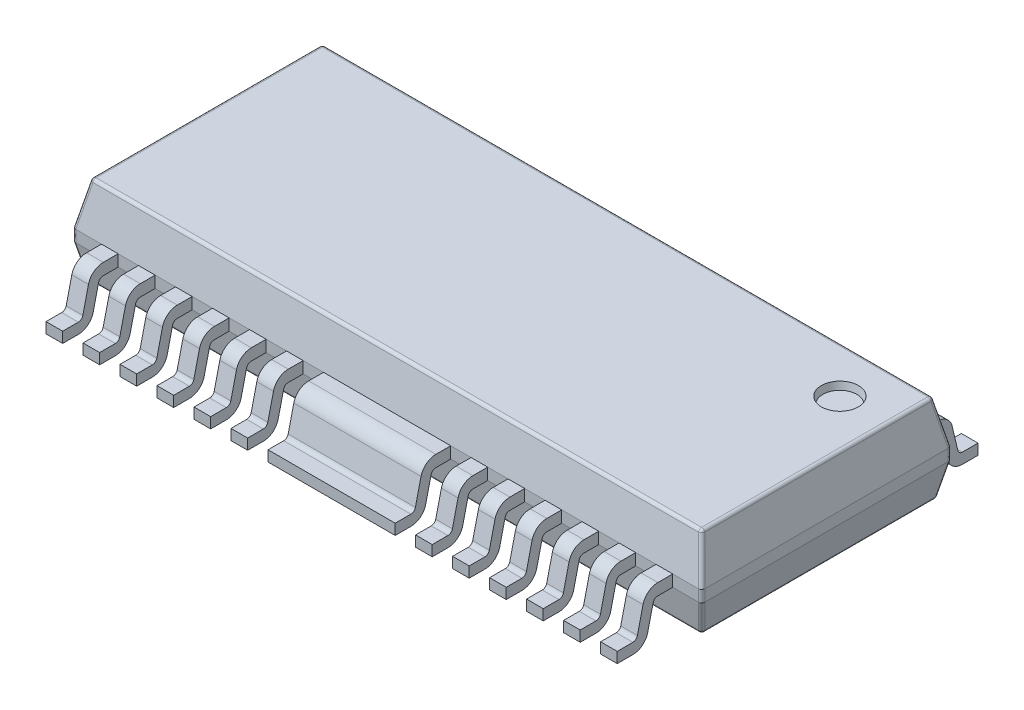
SolidWorks part; units mm, degrees
note: '?' marks a value the reader was unsure of.
ref_plane "Front Plane" through (0, 0, 0) normal (0, 0, 1) x (1, 0, 0)
ref_plane "Top Plane" through (0, 0, 0) normal (0, 1, 0) x (1, 0, 0)
ref_plane "Right Plane" through (0, 0, 0) normal (1, 0, 0) x (0, 0, -1)
ref_axis "Axis1" through (7.48, 0, 0) along (-1, 0, 0)?
ref_plane "Plane1" through (-1.995, 0, 0) normal (1, 0, 0) x (0, 0, -1)
ref_plane "Plane2" through (1.995, 0, 0) normal (1, 0, 0) x (0, 0, -1)
sketch "Sketch1" plane through (0, 0, 0) normal (0, 1, 0) x (1, 0, 0)
  line L1 (-6.8, 2.7) -> (6.8, 2.7)
  line L2 (-6.8, 2.7) -> (-6.8, -2.7)
  line L3 (-6.8, -2.7) -> (6.8, -2.7)
  line L4 (6.8, 2.7) -> (6.8, -2.7)
  dimension "D1" = 13.6
  dimension "D2" = 5.4
  dimension "D3" = 6.8
  dimension "D4" = 2.7
extrude "Extrude1" add sketch "Sketch1" along normal blind 0.93 draft 12 and the other way blind 0.25
sketch "Sketch2" plane through (0, -0.25, 0) normal (0, -1, 0) x (1, 0, 0)
  line L4 (-6.8, 2.7) -> (-6.8, -2.7)
  line L5 (-6.8, -2.7) -> (6.8, -2.7)
  line L6 (6.8, -2.7) -> (6.8, 2.7)
  line L7 (6.8, 2.7) -> (-6.8, 2.7)
  line L8 (-6.8, 2.7) -> (-6.8, -2.7)
  line L9 (-6.8, -2.7) -> (6.8, -2.7)
  line L10 (6.8, -2.7) -> (6.8, 2.7)
  line L11 (6.8, 2.7) -> (-6.8, 2.7)
  dimension "D1" = 0
extrude "Extrude2" add sketch "Sketch2" along normal blind 0.72 draft 12
sketch "Sketch3" plane through (0, 0.93, 0) normal (0, 1, 0) x (-1, 0, 0)
  circle A0 centre (-5.5841, -1.505) radius 0.4
extrude "Cut-Extrude1" cut sketch "Sketch3" against normal blind 0.15 draft 12
sketch "Sketch4" plane through (-1.995, 0, 0) normal (1, 0, 0) x (0, 0, -1)
  line L0 (2.7, -0.25) -> (-2.7, -0.25) construction
  line L1 (2.7, 0) -> (-2.7, 0) construction
  line L2 (2.7, -0.25) -> (-2.7, -0.25)
  line L3 (2.7, 0) -> (-2.7, 0)
  line L4 (-2.547, -0.97) -> (2.547, -0.97) construction
  line L5 (3.9, -0.85) -> (3.4822, -0.85)
  line L6 (3.9, -0.85) -> (3.9, -1.08)
  line L7 (3.9, -1.08) -> (3.3, -1.08)
  line L8 (3.6, -0.85) -> (3.6, -1.08) construction
  line L9 (-2.155, -0.85) -> (-3.4822, -0.85) construction
  line L10 (-2.155, -0.85) -> (-2.155, -1.08) construction
  line L11 (-2.155, -1.08) -> (-3.3, -1.08) construction
  line L12 (-3.9, -0.85) -> (-3.9, -1.08)
  line L13 (2.7, 0) -> (3.2822, 0)
  line L14 (2.6703, 0) -> (2.6703, -0.25) construction
  line L15 (2.6703, -0.25) -> (3.1047, -0.25) construction
  line L16 (-2.7, 0) -> (-3.2822, 0)
  line L17 (-2.6934, 0) -> (-2.6934, -0.25) construction
  line L18 (-2.6934, -0.25) -> (-3.1047, -0.25) construction
  line L19 (3.2822, 0) -> (2.6703, 0) construction
  line L20 (3.4822, -0.85) -> (3.2822, 0)
  line L21 (3.3, -1.08) -> (3.1047, -0.25)
  line L22 (3.1047, -0.25) -> (2.7, -0.25)
  line L23 (3.3, -1.08) -> (3.6, -1.08) construction
  line L24 (3.4822, -0.85) -> (3.6, -0.85) construction
  line L25 (0, -1.1578) -> (0, -1.9582) construction
  line L26 (-3.3, -1.08) -> (-3.1047, -0.25)
  line L27 (-3.4822, -0.85) -> (-3.2822, 0)
  line L28 (-3.1047, -0.25) -> (-2.7, -0.25)
  line L29 (-3.2822, 0) -> (-2.6934, 0) construction
  line L30 (-3.4822, -0.85) -> (-3.9, -0.85)
  line L31 (-3.3, -1.08) -> (-3.9, -1.08)
  dimension "D1" = 0.3
  dimension "D2" = 7.8
  dimension "D3" = 3.9
  dimension "D4" = 0.11
  dimension "D5" = 0.23
  dimension "D6" = 0.23
  dimension "D7" = 0.6
  dimension "D8" = 0.2
extrude "Extrude3" add sketch "Sketch4" along normal blind 0.18 and the other way blind 0.18
pattern_linear "LPattern3" count 1 spacing 0.8 along (-1, 0, 0) count 6 spacing 0.8 along (-1, 0, 0) of "Extrude3"
sketch "Sketch5" plane through (1.995, 0, 0) normal (1, 0, 0) x (0, 0, -1)
  line L16 (3.9, -0.85) -> (3.4822, -0.85)
  line L17 (3.9, -1.08) -> (3.9, -0.85)
  line L18 (3.3, -1.08) -> (3.9, -1.08)
  line L19 (3.1047, -0.25) -> (3.3, -1.08)
  line L20 (2.7, -0.25) -> (3.1047, -0.25)
  line L21 (-2.7, -0.25) -> (2.7, -0.25)
  line L22 (-3.1047, -0.25) -> (-2.7, -0.25)
  line L23 (-3.3, -1.08) -> (-3.1047, -0.25)
  line L24 (-3.9, -1.08) -> (-3.3, -1.08)
  line L25 (-3.9, -0.85) -> (-3.9, -1.08)
  line L26 (-3.4822, -0.85) -> (-3.9, -0.85)
  line L27 (-3.2822, 0) -> (-3.4822, -0.85)
  line L28 (-2.7, 0) -> (-3.2822, 0)
  line L29 (2.7, 0) -> (-2.7, 0)
  line L30 (3.2822, 0) -> (2.7, 0)
  line L31 (3.4822, -0.85) -> (3.2822, 0)
  line L32 (3.9, -0.85) -> (3.4822, -0.85)
  line L33 (3.9, -1.08) -> (3.9, -0.85)
  line L34 (3.3, -1.08) -> (3.9, -1.08)
  line L35 (3.1047, -0.25) -> (3.3, -1.08)
  line L36 (2.7, -0.25) -> (3.1047, -0.25)
  line L37 (-2.7, -0.25) -> (2.7, -0.25)
  line L38 (-3.1047, -0.25) -> (-2.7, -0.25)
  line L39 (-3.3, -1.08) -> (-3.1047, -0.25)
  line L40 (-3.9, -1.08) -> (-3.3, -1.08)
  line L41 (-3.9, -0.85) -> (-3.9, -1.08)
  line L42 (-3.4822, -0.85) -> (-3.9, -0.85)
  line L43 (-3.2822, 0) -> (-3.4822, -0.85)
  line L44 (-2.7, 0) -> (-3.2822, 0)
  line L45 (2.7, 0) -> (-2.7, 0)
  line L46 (3.2822, 0) -> (2.7, 0)
  line L47 (3.4822, -0.85) -> (3.2822, 0)
  dimension "D1" = 0
sketch "Sketch6" plane through (0, 0, 0) normal (1, 0, 0) x (0, 0, -1)
  line L16 (3.9, -0.85) -> (3.4822, -0.85)
  line L17 (3.9, -1.08) -> (3.9, -0.85)
  line L18 (3.3, -1.08) -> (3.9, -1.08)
  line L19 (3.1047, -0.25) -> (3.3, -1.08)
  line L20 (2.7, -0.25) -> (3.1047, -0.25)
  line L21 (-2.7, -0.25) -> (2.7, -0.25)
  line L22 (-3.1047, -0.25) -> (-2.7, -0.25)
  line L23 (-3.3, -1.08) -> (-3.1047, -0.25)
  line L24 (-3.9, -1.08) -> (-3.3, -1.08)
  line L25 (-3.9, -0.85) -> (-3.9, -1.08)
  line L26 (-3.4822, -0.85) -> (-3.9, -0.85)
  line L27 (-3.2822, 0) -> (-3.4822, -0.85)
  line L28 (-2.7, 0) -> (-3.2822, 0)
  line L29 (2.7, 0) -> (-2.7, 0)
  line L30 (3.2822, 0) -> (2.7, 0)
  line L31 (3.4822, -0.85) -> (3.2822, 0)
  line L32 (3.9, -0.85) -> (3.4822, -0.85)
  line L33 (3.9, -1.08) -> (3.9, -0.85)
  line L34 (3.3, -1.08) -> (3.9, -1.08)
  line L35 (3.1047, -0.25) -> (3.3, -1.08)
  line L36 (2.7, -0.25) -> (3.1047, -0.25)
  line L37 (-2.7, -0.25) -> (2.7, -0.25)
  line L38 (-3.1047, -0.25) -> (-2.7, -0.25)
  line L39 (-3.3, -1.08) -> (-3.1047, -0.25)
  line L40 (-3.9, -1.08) -> (-3.3, -1.08)
  line L41 (-3.9, -0.85) -> (-3.9, -1.08)
  line L42 (-3.4822, -0.85) -> (-3.9, -0.85)
  line L43 (-3.2822, 0) -> (-3.4822, -0.85)
  line L44 (-2.7, 0) -> (-3.2822, 0)
  line L45 (2.7, 0) -> (-2.7, 0)
  line L46 (3.2822, 0) -> (2.7, 0)
  line L47 (3.4822, -0.85) -> (3.2822, 0)
  dimension "D1" = 0
extrude "Extrude5" add sketch "Sketch6" along normal blind 1.375 and the other way blind 1.375
extrude "Extrude6" add sketch "Sketch5" along normal blind 0.18 and the other way blind 0.18
pattern_linear "LPattern4" count 6 spacing 0.8 along (1, 0, 0) of "Extrude6"
fillet "Fillet2" radius 0.33 52 edges at (-2.795, -1.08, -3.3) (-2.795, 0, 3.2822) (-2.795, -1.08, 3.3) (-3.595, 0, -3.2822) (-3.595, -1.08, -3.3) (-3.595, 0, 3.2822) (-3.595, -1.08, 3.3) (-4.395, 0, -3.2822) (-4.395, -1.08, -3.3) (-4.395, 0, 3.2822) (-4.395, -1.08, 3.3) (-5.195, 0, -3.2822) (-5.195, -1.08, -3.3) (-5.195, 0, 3.2822) (-5.195, -1.08, 3.3) (-5.995, 0, -3.2822) (-5.995, -1.08, -3.3) (-5.995, 0, 3.2822) (-5.995, -1.08, 3.3) (0, 0, -3.2822) (0, 0, 3.2822) (0, -1.08, 3.3) (0, -1.08, -3.3) (1.995, 0, -3.2822) (1.995, 0, 3.2822) (1.995, -1.08, 3.3) (1.995, -1.08, -3.3) (2.795, 0, -3.2822) (2.795, 0, 3.2822) (2.795, -1.08, 3.3) (2.795, -1.08, -3.3) (-1.995, 0, -3.2822) (3.595, 0, -3.2822) (3.595, 0, 3.2822) (3.595, -1.08, 3.3) (3.595, -1.08, -3.3) (4.395, 0, -3.2822) (4.395, 0, 3.2822) (4.395, -1.08, 3.3) (4.395, -1.08, -3.3) (-1.995, -1.08, -3.3) (5.195, 0, -3.2822) (-1.995, 0, 3.2822) (5.195, 0, 3.2822) (5.195, -1.08, 3.3) (5.195, -1.08, -3.3) (-1.995, -1.08, 3.3) (5.995, 0, -3.2822) (5.995, 0, 3.2822) (5.995, -1.08, 3.3) (5.995, -1.08, -3.3) (-2.795, 0, -3.2822)
fillet "Fillet1" radius 0.1 52 edges at (-1.995, -0.85, 3.4822) (-1.995, -0.25, 3.1047) (-1.995, -0.85, -3.4822) (-1.995, -0.25, -3.1047) (-4.395, -0.85, 3.4822) (-3.595, -0.85, 3.4822) (-2.795, -0.85, 3.4822) (-2.795, -0.85, -3.4822) (-3.595, -0.85, -3.4822) (-4.395, -0.85, -3.4822) (-4.395, -0.25, 3.1047) (-3.595, -0.25, 3.1047) (-2.795, -0.25, 3.1047) (-4.395, -0.25, -3.1047) (-3.595, -0.25, -3.1047) (-2.795, -0.25, -3.1047) (5.995, -0.25, 3.1047) (5.195, -0.25, 3.1047) (4.395, -0.25, 3.1047) (3.595, -0.25, 3.1047) (2.795, -0.25, 3.1047) (1.995, -0.25, 3.1047) (0, -0.25, 3.1047) (-5.995, -0.25, 3.1047) (-5.195, -0.25, 3.1047) (-5.995, -0.25, -3.1047) (-5.195, -0.25, -3.1047) (0, -0.25, -3.1047) (1.995, -0.25, -3.1047) (2.795, -0.25, -3.1047) (3.595, -0.25, -3.1047) (4.395, -0.25, -3.1047) (5.195, -0.25, -3.1047) (5.995, -0.25, -3.1047) (-5.995, -0.85, -3.4822) (-5.195, -0.85, -3.4822) (0, -0.85, -3.4822) (1.995, -0.85, -3.4822) (2.795, -0.85, -3.4822) (3.595, -0.85, -3.4822) (4.395, -0.85, -3.4822) (5.195, -0.85, -3.4822) (5.995, -0.85, -3.4822) (5.995, -0.85, 3.4822) (5.195, -0.85, 3.4822) (4.395, -0.85, 3.4822) (3.595, -0.85, 3.4822) (2.795, -0.85, 3.4822) (1.995, -0.85, 3.4822) (0, -0.85, 3.4822) (-5.195, -0.85, 3.4822) (-5.995, -0.85, 3.4822)
fillet "Fillet3" radius 0.07 20 edges at (6.6023, 0.93, 0) (-6.8, -0.125, 2.7) (0, 0.93, -2.5023) (-6.8, -0.125, -2.7) (6.8, -0.125, -2.7) (6.8, -0.125, 2.7) (6.7235, -0.61, 2.6235) (-6.7235, -0.61, 2.6235) (-6.7235, -0.61, -2.6235) (6.7235, -0.61, -2.6235) (0, -0.97, 2.547) (-6.647, -0.97, 0) (0, -0.97, -2.547) (6.647, -0.97, 0) (-6.6023, 0.93, 0) (0, 0.93, 2.5023) (-6.7012, 0.465, -2.6012) (6.7012, 0.465, -2.6012) (6.7012, 0.465, 2.6012) (-6.7012, 0.465, 2.6012)
ref_plane "Board Surface" through (0, -1.08, 0) normal (0, 1, 0) x (-1, 0, 0)
sketch "Component_Outline" plane through (0, -1.08, 0) normal (0, 1, 0) x (-1, 0, 0)
  line L0 (6.175, 3.9) -> (5.815, 3.9)
  line L1 (5.815, 3.9) -> (5.815, 2.7)
  line L2 (5.815, 2.7) -> (5.375, 2.7)
  line L3 (5.375, 2.7) -> (5.375, 3.9)
  line L4 (5.375, 3.9) -> (5.015, 3.9)
  line L5 (5.015, 3.9) -> (5.015, 2.7)
  line L6 (5.015, 2.7) -> (4.575, 2.7)
  line L7 (4.575, 2.7) -> (4.575, 3.9)
  line L8 (4.575, 3.9) -> (4.215, 3.9)
  line L9 (4.215, 3.9) -> (4.215, 2.7)
  line L10 (4.215, 2.7) -> (3.775, 2.7)
  line L11 (3.775, 2.7) -> (3.775, 3.9)
  line L12 (3.775, 3.9) -> (3.415, 3.9)
  line L13 (3.415, 3.9) -> (3.415, 2.7)
  line L14 (3.415, 2.7) -> (2.975, 2.7)
  line L15 (2.975, 2.7) -> (2.975, 3.9)
  line L16 (2.975, 3.9) -> (2.615, 3.9)
  line L17 (2.615, 3.9) -> (2.615, 2.7)
  line L18 (2.615, 2.7) -> (2.175, 2.7)
  line L19 (2.175, 2.7) -> (2.175, 3.9)
  line L20 (2.175, 3.9) -> (1.815, 3.9)
  line L21 (1.815, 3.9) -> (1.815, 2.7)
  line L22 (1.815, 2.7) -> (1.375, 2.7)
  line L23 (1.375, 2.7) -> (1.375, 3.9)
  line L24 (6.175, 2.7) -> (6.175, 3.9)
  line L25 (-1.375, 3.9) -> (-1.375, 2.7)
  line L26 (-1.375, 2.7) -> (-1.815, 2.7)
  line L27 (-1.815, 2.7) -> (-1.815, 3.9)
  line L28 (-1.815, 3.9) -> (-2.175, 3.9)
  line L29 (-2.175, 3.9) -> (-2.175, 2.7)
  line L30 (-2.175, 2.7) -> (-2.615, 2.7)
  line L31 (-2.615, 2.7) -> (-2.615, 3.9)
  line L32 (-2.615, 3.9) -> (-2.975, 3.9)
  line L33 (-2.975, 3.9) -> (-2.975, 2.7)
  line L34 (-2.975, 2.7) -> (-3.415, 2.7)
  line L35 (-3.415, 2.7) -> (-3.415, 3.9)
  line L36 (-3.415, 3.9) -> (-3.775, 3.9)
  line L37 (-3.775, 3.9) -> (-3.775, 2.7)
  line L38 (-3.775, 2.7) -> (-4.215, 2.7)
  line L39 (-4.215, 2.7) -> (-4.215, 3.9)
  line L40 (-4.215, 3.9) -> (-4.575, 3.9)
  line L41 (-4.575, 3.9) -> (-4.575, 2.7)
  line L42 (-4.575, 2.7) -> (-5.015, 2.7)
  line L43 (-5.015, 2.7) -> (-5.015, 3.9)
  line L44 (-5.015, 3.9) -> (-5.375, 3.9)
  line L45 (-5.375, 3.9) -> (-5.375, 2.7)
  line L46 (-5.375, 2.7) -> (-5.815, 2.7)
  line L47 (-5.815, 2.7) -> (-5.815, 3.9)
  line L48 (-5.815, 3.9) -> (-6.175, 3.9)
  line L49 (-6.175, 3.9) -> (-6.175, 2.7)
  line L50 (1.375, 3.9) -> (-1.375, 3.9)
  line L51 (6.8, 0) -> (-6.8, 0) construction
  line L52 (6.8, -2.63) -> (6.8, 2.63) construction
  line L53 (-6.8, 2.63) -> (-6.8, -2.63) construction
  line L54 (1.375, -3.9) -> (-1.375, -3.9)
  line L55 (-6.175, -3.9) -> (-6.175, -2.7)
  line L56 (-5.815, -3.9) -> (-6.175, -3.9)
  line L57 (-5.815, -2.7) -> (-5.815, -3.9)
  line L58 (-5.375, -2.7) -> (-5.815, -2.7)
  line L59 (-5.375, -3.9) -> (-5.375, -2.7)
  line L60 (-5.015, -3.9) -> (-5.375, -3.9)
  line L61 (-5.015, -2.7) -> (-5.015, -3.9)
  line L62 (-4.575, -2.7) -> (-5.015, -2.7)
  line L63 (-4.575, -3.9) -> (-4.575, -2.7)
  line L64 (-4.215, -3.9) -> (-4.575, -3.9)
  line L65 (-4.215, -2.7) -> (-4.215, -3.9)
  line L66 (-3.775, -2.7) -> (-4.215, -2.7)
  line L67 (-3.775, -3.9) -> (-3.775, -2.7)
  line L68 (-3.415, -3.9) -> (-3.775, -3.9)
  line L69 (-3.415, -2.7) -> (-3.415, -3.9)
  line L70 (-2.975, -2.7) -> (-3.415, -2.7)
  line L71 (-2.975, -3.9) -> (-2.975, -2.7)
  line L72 (-2.615, -3.9) -> (-2.975, -3.9)
  line L73 (-2.615, -2.7) -> (-2.615, -3.9)
  line L74 (-2.175, -2.7) -> (-2.615, -2.7)
  line L75 (-2.175, -3.9) -> (-2.175, -2.7)
  line L76 (-1.815, -3.9) -> (-2.175, -3.9)
  line L77 (-1.815, -2.7) -> (-1.815, -3.9)
  line L78 (-1.375, -2.7) -> (-1.815, -2.7)
  line L79 (-1.375, -3.9) -> (-1.375, -2.7)
  line L80 (6.175, -2.7) -> (6.175, -3.9)
  line L81 (1.375, -2.7) -> (1.375, -3.9)
  line L82 (1.815, -2.7) -> (1.375, -2.7)
  line L83 (1.815, -3.9) -> (1.815, -2.7)
  line L84 (2.175, -3.9) -> (1.815, -3.9)
  line L85 (2.175, -2.7) -> (2.175, -3.9)
  line L86 (2.615, -2.7) -> (2.175, -2.7)
  line L87 (2.615, -3.9) -> (2.615, -2.7)
  line L88 (2.975, -3.9) -> (2.615, -3.9)
  line L89 (2.975, -2.7) -> (2.975, -3.9)
  line L90 (3.415, -2.7) -> (2.975, -2.7)
  line L91 (3.415, -3.9) -> (3.415, -2.7)
  line L92 (3.775, -3.9) -> (3.415, -3.9)
  line L93 (3.775, -2.7) -> (3.775, -3.9)
  line L94 (4.215, -2.7) -> (3.775, -2.7)
  line L95 (4.215, -3.9) -> (4.215, -2.7)
  line L96 (4.575, -3.9) -> (4.215, -3.9)
  line L97 (4.575, -2.7) -> (4.575, -3.9)
  line L98 (5.015, -2.7) -> (4.575, -2.7)
  line L99 (5.015, -3.9) -> (5.015, -2.7)
  line L100 (5.375, -3.9) -> (5.015, -3.9)
  line L101 (5.375, -2.7) -> (5.375, -3.9)
  line L102 (5.815, -2.7) -> (5.375, -2.7)
  line L103 (5.815, -3.9) -> (5.815, -2.7)
  line L104 (6.175, -3.9) -> (5.815, -3.9)
  line L105 (6.175, -2.7) -> (6.8, -2.7)
  line L106 (6.8, -2.7) -> (6.8, 2.7)
  line L107 (6.8, 2.7) -> (6.175, 2.7)
  line L108 (-6.175, -2.7) -> (-6.8, -2.7)
  line L109 (-6.8, -2.7) -> (-6.8, 2.7)
  line L110 (-6.8, 2.7) -> (-6.175, 2.7)
  line L111 (-6.8, 2.63) -> (-6.8, -2.63) construction
  point P168 (0, 0)
